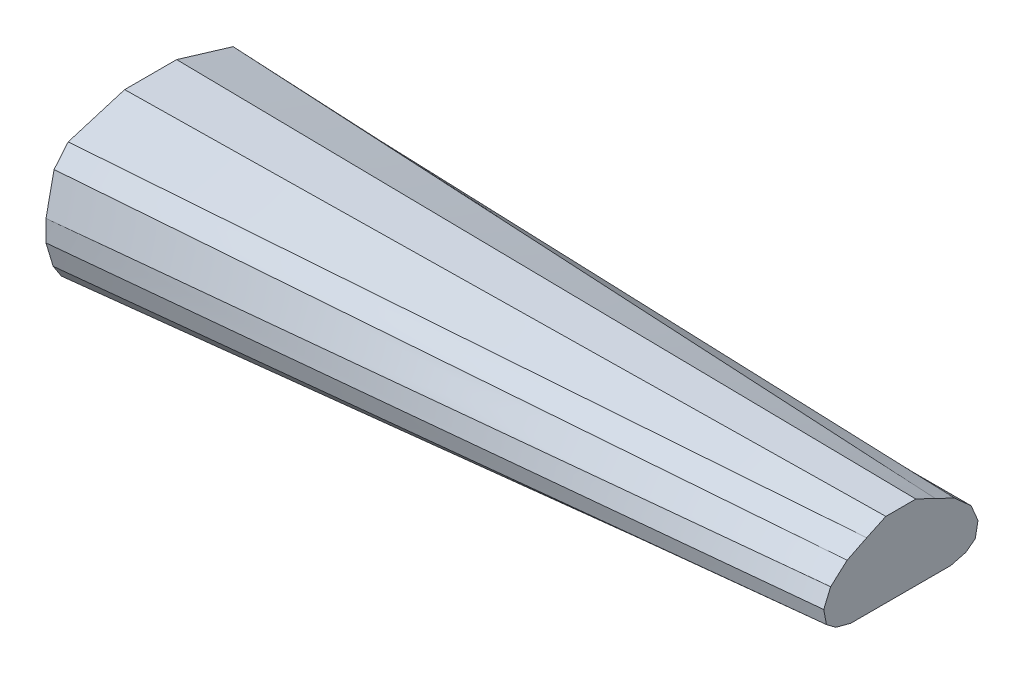
SolidWorks part; units mm, degrees
material "AISI 304"
ref_plane "Front Plane" through (0, 0, 0) normal (0, 0, 1) x (1, 0, 0)
ref_plane "Top Plane" through (0, 0, 0) normal (0, 1, 0) x (1, 0, 0)
ref_plane "Right Plane" through (0, 0, 0) normal (1, 0, 0) x (0, 0, -1)
ref_plane "Plane1" through (15000, 0, 0) normal (1, 0, 0) x (0, 0, -1)
sketch "Sketch8" plane through (0, 0, 0) normal (1, 0, 0) x (0, 0, -1)
  line L1 (0, 0) -> (0, 4451.7248) construction
  line L8 (-519.8932, 3511.9436) -> (519.8932, 3511.9436)
  line L18 (-1260.4384, 600) -> (1260.4384, 600)
  line L32 (-1260.4384, 600) -> (-1785.1323, 914.8774)
  line L33 (-1785.1323, 914.8774) -> (-1948.859, 1166.2608)
  line L34 (-1948.859, 1166.2608) -> (-2092.7308, 1643.2495)
  line L35 (-2092.7308, 1643.2495) -> (-2092.7308, 2069.0866)
  line L36 (-2092.7308, 2069.0866) -> (-1931.2321, 2833.8849)
  line L37 (-1931.2321, 2833.8849) -> (-1648.7298, 3171.4581)
  line L38 (-1648.7298, 3171.4581) -> (-519.8932, 3511.9436)
  line L39 (1648.7298, 3171.4581) -> (519.8932, 3511.9436)
  line L41 (1931.2321, 2833.8849) -> (1648.7298, 3171.4581)
  line L48 (2092.7308, 2069.0866) -> (1931.2321, 2833.8849)
  line L49 (2092.7308, 1643.2495) -> (2092.7308, 2069.0866)
  line L50 (1948.859, 1166.2608) -> (2092.7308, 1643.2495)
  line L51 (1785.1323, 914.8774) -> (1948.859, 1166.2608)
  line L52 (1260.4384, 600) -> (1785.1323, 914.8774)
  point P5 (0, 3511.9436)
  point P42 (0, 600)
  dimension "D1" = 163.215
  dimension "D2" = 300
  dimension "D3" = 146.709
  dimension "D4" = 168.076
  dimension "D5" = 163.215
  dimension "D6" = 163.708
  dimension "D7" = 154.045
  dimension "D8" = 149.031
  dimension "D9" = 2520.8768
sketch "Sketch9" plane through (15000, 0, 0) normal (1, 0, 0) x (0, 0, -1)
  line L0 (-300, 3511.9436) -> (300, 3511.9436)
  line L1 (0, 0) -> (0, 4451.7248) construction
  line L27 (-519.8932, 3511.9436) -> (519.8932, 3511.9436) construction
  line L35 (-1000, 2011.9436) -> (1000, 2011.9436)
  line L36 (1000, 2011.9436) -> (1299.7666, 2090.3368)
  line L37 (1299.7666, 2090.3368) -> (1487.5377, 2231.6926)
  line L38 (1487.5377, 2231.6926) -> (1542.3006, 2520.7853)
  line L39 (1542.3006, 2520.7853) -> (1403.885, 2845.1967)
  line L40 (1403.885, 2845.1967) -> (1075.1481, 3139.3297)
  line L41 (1075.1481, 3139.3297) -> (683.7086, 3333.0019)
  line L42 (683.7086, 3333.0019) -> (300, 3511.9436)
  line L44 (-1000, 2011.9436) -> (-1299.7666, 2090.3368)
  line L45 (-1299.7666, 2090.3368) -> (-1487.5377, 2231.6926)
  line L46 (-1487.5377, 2231.6926) -> (-1542.3006, 2520.7853)
  line L47 (-1542.3006, 2520.7853) -> (-1403.885, 2845.1967)
  line L48 (-1403.885, 2845.1967) -> (-1075.1481, 3139.3297)
  line L49 (-1075.1481, 3139.3297) -> (-683.7086, 3333.0019)
  line L50 (-683.7086, 3333.0019) -> (-300, 3511.9436)
  point P6 (0, 3511.9436)
  point P9 (0, 2011.9436)
  point P15 (0, 961.9436)
  dimension "D1" = 2000
  dimension "D2" = 1500
  dimension "D3" = 600
loft "Loft3" add profiles "Sketch8", "Sketch9" connector at (0, 3171.4581, 1648.7298) connector at (15000, 3333.0019, 683.7086)
shell "Shell2" thickness 100 removed face at (0, 1988.8451, 0)
sketch "Sketch10" plane through (-55.9817, 594.7305, 0) normal (0.0937, -0.9956, 0) x (0.9956, 0.0937, 0)
  line L0 (56.2292, 1260.4384) -> (15122.5355, 1000)
  line L1 (15122.5355, 1000) -> (15122.5355, -1000)
  line L2 (15122.5355, -1000) -> (56.2292, -1260.4384)
  line L3 (56.2292, -1260.4384) -> (56.2292, 1260.4384)
extrude "Cut-Extrude1" cut sketch "Sketch10" against normal blind 100
